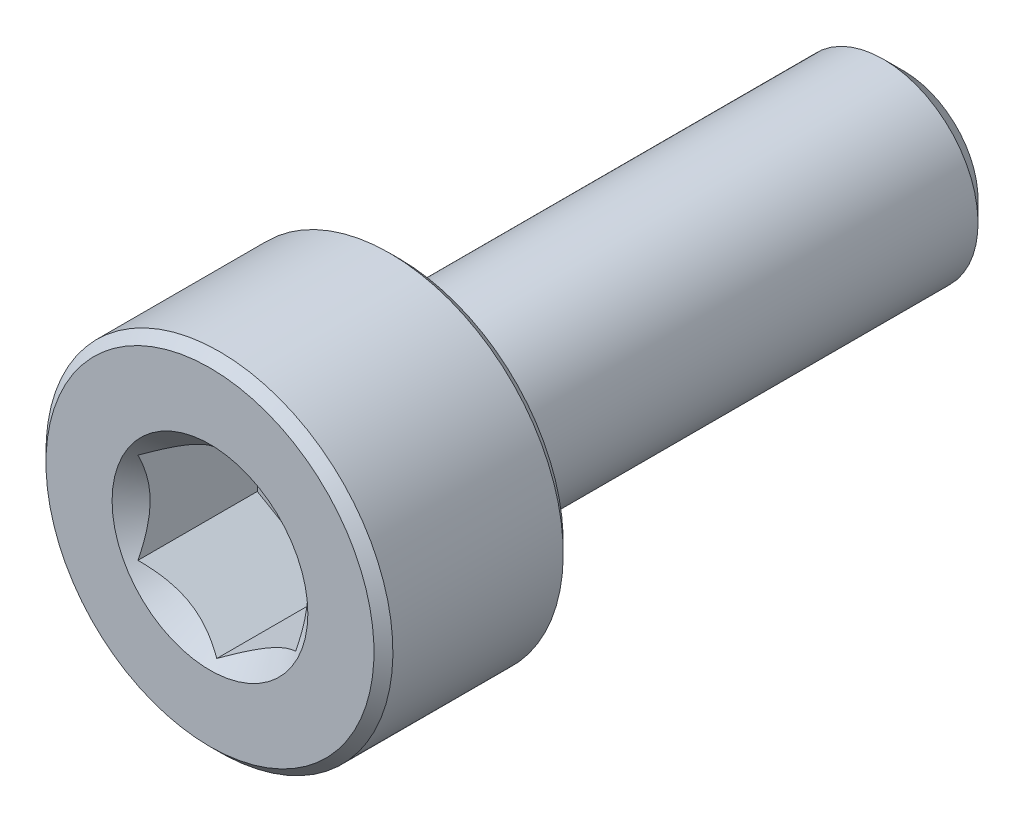
SolidWorks part; units mm, degrees
material "Alloy Steel (SS)"
ref_plane "Front Plane" through (0, 0, 0) normal (0, 0, 1) x (1, 0, 0)
ref_plane "Top Plane" through (0, 0, 0) normal (0, 1, 0) x (1, 0, 0)
ref_plane "Right Plane" through (0, 0, 0) normal (1, 0, 0) x (0, 0, -1)
sketch "Sketch1" plane through (0, 0, 0) normal (1, 0, 0) x (0, 0, -1)
  line L0 (-5.5, 0) -> (5.5, 0) construction
  line L1 (5.5, 0) -> (5.5, 1.1752) construction
  line L2 (5.5, 1.1752) -> (5.1752, 1.5) construction
  line L3 (5.1752, 1.5) -> (5.125, 1.5) construction
  line L4 (5.125, 1.5) -> (-2.5, 1.5) construction
  line L5 (-2.5, 1.5) -> (-2.5, 2.75) construction
  line L6 (-2.5, 2.75) -> (-5.5, 2.75) construction
  line L7 (-5.5, 2.75) -> (-5.5, 0) construction
  line L8 (5.5, 1.1752) -> (5.5, 1.5) construction
  line L9 (5.4687, 1.5541) -> (5.7187, 1.1211) construction
  line L10 (5.7187, 1.1211) -> (5.9687, 1.5541) construction
  line L11 (5.9687, 1.5541) -> (5.4687, 1.5541) construction
  line L12 (5.7187, 1.5541) -> (5.7187, 1.5) construction
  line L13 (5.7187, 1.1211) -> (5.7187, 1.1752) construction
  line L14 (5.6875, 1.1752) -> (5.75, 1.1752) construction
  line L15 (5.5, 1.5) -> (5.9375, 1.5) construction
  line L16 (5.4844, 1.5271) -> (5.9531, 1.5271) construction
  line L17 (5.5, 0) -> (5.5, -1.5) construction
  line L18 (-2.65, 2.75) -> (-2.5, 2.6) construction
  line L19 (-5.35, 2.75) -> (-5.5, 2.6) construction
  line L20 (-2.5, 1.5) -> (-2.5, 0) construction
  line L21 (-2.5, 0.75) -> (0.1667, 0.75) construction
  line L22 (0.1667, 0.75) -> (2.8333, 0.75) construction
  line L23 (2.8333, 0.75) -> (5.5, 0.75) construction
  line L24 (0.1667, 0.75) -> (0.1667, 1.5) construction
  line L25 (0.1667, 1.5) -> (0.1667, 2.75) construction
  line L26 (2.8333, 0.75) -> (2.8333, 2.75) construction
  point P0 (-5.5, 1.25)
  point P3 (4.25, 1.5)
  point P4 (0, 0)
  point P18 (2.8333, 1.5)
  point P22 (5.7187, 1.1752)
  point P24 (5.125, 1.5)
  point P25 (5.7187, 1.5)
  point P28 (5.7187, 1.5271)
  point P29 (4.25, -1.5)
  point P30 (0.1667, 1.5)
  point P31 (-4, 2.75)
  point P37 (-3.025, 2.75)
  point P38 (-5.275, 2.75)
  point P45 (0.1667, 0.75)
  point P46 (2.8333, 0.75)
  dimension "D2" = 0.0625
  dimension "D7" = 0.15
  dimension "D8" = 0.15
  dimension "D9" = 0.15
  dimension "D10" = 0.075
  dimension "D11" = 0.375
  dimension "Drive Size" = 2.5
  dimension "Head Diameter" = 5.5
  dimension "Head Height" = 3
  dimension "Thread Pitch" = 0.5
  dimension "Thread Dia" = 3
  dimension "Length" = 8
  dimension "D12" = 0.375
  dimension "D4" = 1.25
  dimension "D3" = 45
sketch "Sketch2" plane through (0, 0, 0) normal (1, 0, 0) x (0, 0, -1)
  line L0 (-5.5, 0) -> (-5.5, 2.6)
  line L1 (-5.35, 2.75) -> (-2.65, 2.75)
  line L2 (-2.5, 2.6) -> (-2.5, 1.65)
  line L4 (5.1752, 1.5) -> (5.5, 1.1752)
  line L5 (5.5, 1.1752) -> (5.5, 0)
  line L6 (-2.5, 2.75) -> (-5.5, 2.75) construction
  line L7 (5.5, 0) -> (-5.5, 0)
  line L8 (-5.35, 2.75) -> (-5.5, 2.6) construction
  line L10 (-5.35, 2.75) -> (-5.5, 2.6)
  line L14 (-2.65, 2.75) -> (-2.5, 2.6) construction
  line L16 (-2.65, 2.75) -> (-2.5, 2.6)
  line L17 (-2.5, 1.5) -> (-2.5, 2.75) construction
  line L19 (-2.35, 1.5) -> (5.1752, 1.5)
  line L20 (5.125, 1.5) -> (-2.5, 1.5) construction
  arc A1 (-2.5, 1.65) -> (-2.35, 1.5) centre (-2.35, 1.65) ccw
  dimension "D3" = 0.15
revolve "Revolve1" add sketch "Sketch2" angle 360 about L7
sketch "Sketch3" plane through (0, 0, 5.5) normal (0, 0, 1) x (1, 0, 0)
  line L1 (1.25, -0.7217) -> (1.25, 0.7217)
  line L2 (1.25, 0.7217) -> (0, 1.4434)
  line L3 (0, 1.4434) -> (-1.25, 0.7217)
  line L4 (-1.25, 0.7217) -> (-1.25, -0.7217)
  line L5 (-1.25, -0.7217) -> (0, -1.4434)
  line L6 (0, -1.4434) -> (1.25, -0.7217)
  circle A0 centre (0, 0) radius 1.25 construction
  circle A1 centre (0, 0) radius 2.75 construction
  circle A2 centre (0, 0) radius 2.75 construction
  circle A3 centre (0, 0) radius 1.4434 construction
  point P13 (0, 0)
  dimension "D1" = 2.8868
extrude "Cut-Extrude1" cut sketch "Sketch3" against normal offset from surface (2 mm away) 1 up to face at (0, 2.6, 2.5)
sketch "Sketch4" plane through (0, 0, 5.5) normal (0, 0, 1) x (1, 0, 0)
  circle A0 centre (0, 0) radius 1.5516
  dimension "D1" = 3.1033
extrude "Cut-Extrude2" cut sketch "Sketch4" against normal up to vertex (1.5 mm away) draft 45 up to point (0, 2.75, 4)
sketch "Sketch11" plane through (0, 0, 0) normal (1, 0, 0) x (0, 0, -1)
  line L0 (-5.5, 0) -> (5.5, 0) construction
  line L1 (-5.5, 0) -> (5.5, 0) construction
  line L2 (-1, 0) -> (-1, 1.5) construction
  line L3 (5.125, 1.5) -> (-2.5, 1.5) construction
  line L4 (4, 0) -> (4, 1.5) construction
  line L6 (5.5, 1.1752) -> (5.5, 1.5) construction
  point P2 (-1, 0)
  point P3 (4, 0)
  dimension "D1" = 1.5
  dimension "D2" = 1.5
sketch "Sketch6" [suppressed] plane through (0, 0, -5.5) normal (0, 0, -1) x (-1, 0, 0)
  circle A0 centre (0, 0) radius 1.5
curve "Helix/Spiral1" [suppressed] pitch 0.5 height 8.5 turns 17
sketch "Sketch10" [suppressed] plane through (0, 0, 0) normal (1, 0, 0) x (0, 0, -1)
  line L0 (-2.35, -2.75) -> (-2.35, 2.75)
  line L5 (-5.5, 0) -> (5.5, 0) construction
  line L6 (-2.35, 1.5) -> (-2.35, -1.5) construction
  point P3 (-2.35, 0)
split "Split1" [suppressed] bodies to split 106
sketch "Sketch7" [suppressed] plane through (0, 0, 0) normal (1, 0, 0) x (0, 0, -1)
  line L0 (5.4844, 1.5271) -> (5.9531, 1.5271)
  line L1 (5.9531, 1.5271) -> (5.75, 1.1752)
  line L2 (5.75, 1.1752) -> (5.6875, 1.1752)
  line L3 (5.6875, 1.1752) -> (5.4844, 1.5271)
sweep "Cut-Sweep1" [suppressed] cut profiles "Sketch7" path "Helix/Spiral1"
sketch "Sketch8" [suppressed] plane through (0, 0, 0) normal (1, 0, 0) x (0, 0, -1)
  line L0 (-2.5, 0) -> (-2.5, 1.5)
  line L1 (-2.35, -1.5) -> (-2.35, 1.5) construction
  line L2 (-2.5, 1.5) -> (-2.35, 1.5)
  line L4 (-2.35, 1.5) -> (-1.484, 0)
  line L5 (-1.484, 0) -> (-2.5, 0)
  line L6 (5.125, 1.5) -> (-2.5, 1.5) construction
  line L7 (-5.5, 0) -> (5.5, 0) construction
  dimension "D1" = 60
revolve "Revolve2" [suppressed] add sketch "Sketch8" angle 360 about L5
equation "\"D2@Sketch1\" = \"Thread Pitch@Sketch1\" / 8"
equation "\"D4@Helix/Spiral1\" = \"Thread Pitch@Sketch1\""
equation "\"D7@Sketch1\" = \"Head Height@Sketch1\" * .05"
equation "\"D8@Sketch1\"=\"D7@Sketch1\""
equation "\"D9@Sketch1\"=\"D7@Sketch1\""
equation "\"D10@Sketch1\"=\"D7@Sketch1\"/2"
equation "\"D11@Sketch1\"=\"D10@Sketch1\"*5"
equation "\"D4@Sketch1\"=\"Thread Pitch@Sketch1\"*2.5"
equation "\"D12@Sketch1\"=\"Thread Pitch@Sketch1\"*.75"
equation "\"D3@Helix/Spiral1\"=\"Length@Sketch1\"+\"Thread Pitch@Sketch1\""
equation "\"D3@Sketch2\"=\"Thread Dia@Sketch1\"*0.05"
equation "\"D1@Sketch11\"=\"Length@Sketch1\"*0.1875"
equation "\"D2@Sketch11\"=\"D1@Sketch11\""
equation "\"D1@Sketch4\"=\"D1@Sketch3\"*1.075"
